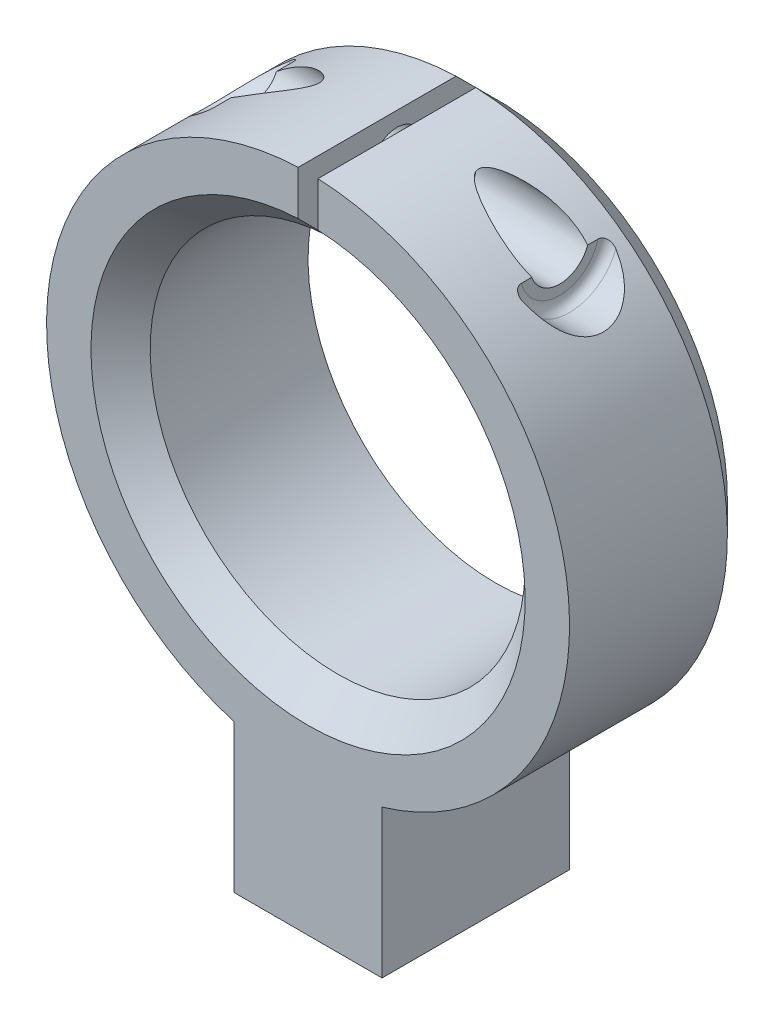
SolidWorks part; units mm, degrees
note: The reader was unsure of these and kept them because the rebuilt part matched: shared geometry of "Sketch5<3>", "Sketch6<3>".
ref_plane "Front Plane" through (0, 0, 0) normal (0, 0, 1) x (1, 0, 0)
ref_plane "Top Plane" through (0, 0, 0) normal (0, 1, 0) x (1, 0, 0)
ref_plane "Right Plane" through (0, 0, 0) normal (1, 0, 0) x (0, 0, -1)
sketch "Sketch1" plane through (0, 0, 0) normal (0, 0, 1) x (1, 0, 0)
  line L0 (-16.7192, 28.2333) -> (-16.7192, 35.7407)
  line L2 (-23.2192, -16.1569) -> (-8.2192, -16.1569)
  line L3 (-23.2192, -16.1569) -> (-23.2192, -31.1569)
  line L4 (-23.2192, -31.1569) -> (-8.2192, -31.1569)
  line L5 (-8.2192, -16.1569) -> (-8.2192, -31.1569)
  line L9 (-16.7192, 35.7407) -> (-14.7192, 35.7407)
  line L10 (-14.7192, 35.7407) -> (-14.7192, 28.2333)
  circle A0 centre (-15.7192, 9.2596) radius 19
  circle A1 centre (-15.7192, 9.2596) radius 26.5
  dimension "D1" = 38
  dimension "D4" = 53
  dimension "D2" = 15
  dimension "D3" = 15
  dimension "D8" = 2
  dimension "D9" = 1
extrude "Boss-Extrude1" add sketch "Sketch1" along normal blind 16
sketch "Sketch2" plane through (0, -31.1569, 0) normal (0, -1, 0) x (1, 0, 0)
  line L0 (-23.2192, 0) -> (-8.2192, 0) construction
  circle A0 centre (-15.7192, 8.5) radius 3.05
  dimension "D1" = 6.1
  dimension "D2" = 8.5
extrude "Cut-Extrude1" cut sketch "Sketch2" against normal blind 15
sketch "Sketch3" plane through (0, 0, 16) normal (0, 0, 1) x (1, 0, 0)
  line L0 (-16.7192, 25.2283) -> (-16.7192, 28.2333)
  line L1 (-14.7192, 28.2333) -> (-14.7192, 25.2283)
  line L2 (-14.7192, 35.7407) -> (-14.7192, 28.2333) construction
  line L3 (-16.7192, 28.2333) -> (-16.7192, 35.7407) construction
  circle A0 centre (-15.7192, 9.2596) radius 16
  circle A1 centre (-15.7192, 9.2596) radius 12.25
  line M4 (-14.7192, 35.7407) -> (-14.7192, 28.2333)
  arc M5 (-14.7192, 28.2333) -> (-16.7192, 28.2333) centre (-15.7192, 9.2596) cw
  line M6 (-16.7192, 28.2333) -> (-16.7192, 35.7407)
  dimension "D1" = 32
extrude "Boss-Extrude2" add sketch "Sketch3" along normal blind 3 contours A0 M6 M4 M5
chamfer "Chamfer4" distance 3 angle 45 3 edges at (10.5754, 12.5529, 0) (-42.0137, 12.5529, 0) (-15.7192, -9.7404, 19)
sketch "Sketch4" plane through (-14.7192, 0, 0) normal (-1, 0, 0) x (0, 0, 1)
  line L0 (0, 32.7383) -> (0, 28.2333) construction
  line L2 (19, 35.7407) -> (3, 35.7407) construction
  circle A0 centre (9, 31.7407) radius 1.5
  dimension "D1" = 3
  dimension "D2" = 9
  dimension "D3" = 4
extrude "Cut-Extrude2" cut sketch "Sketch4" against normal blind 25 and the other way blind 29
ref_plane "Plane1" through (-42.2192, 0, 0) normal (-1, 0, 0) x (0, 0, 1)
sketch "Sketch5" plane through (-42.2192, 0, 0) normal (-1, 0, 0) x (0, 0, 1)
  circle A0 centre (9, 31.7407) radius 2.5
  circle A1 centre (9, 31.7407) radius 5
  dimension "D1" = 5
  dimension "D2" = 10
extrude "Cut-Extrude3" cut sketch "Sketch5" against normal up to surface (27.5 mm away) contours A0 up to face at (-14.7192, 31.7407, 7.5)
ref_plane "Plane2" through (10.7808, 0, 0) normal (1, 0, 0) x (0, 0, -1)
sketch "Sketch6" plane through (10.7808, 0, 0) normal (1, 0, 0) x (0, 0, -1)
  circle A0 centre (-9, 31.7407) radius 3
  circle A1 centre (-9, 31.7407) radius 5
  dimension "D1" = 6
  dimension "D2" = 10
extrude "Cut-Extrude4" cut sketch "Sketch6" against normal offset from surface (22.5 mm away) 5 contours A0 up to face at (-16.7192, 29.2407, 9)
extrude "Cut-Extrude5" cut sketch "Sketch5<3>" against normal blind 11
sketch "Sketch5<3>" plane through (-42.2192, 0, 0) normal (-1, 0, 0) x (0, 0, 1) same geometry as "Sketch5"
extrude "Cut-Extrude6" cut sketch "Sketch6<3>" against normal blind 11
sketch "Sketch6<3>" plane through (10.7808, 0, 0) normal (1, 0, 0) x (0, 0, -1) same geometry as "Sketch6"
fillet "Fillet1" radius 1 2 edges at (-31.2192, 26.7407, 9) (-0.2192, 26.7407, 9)
